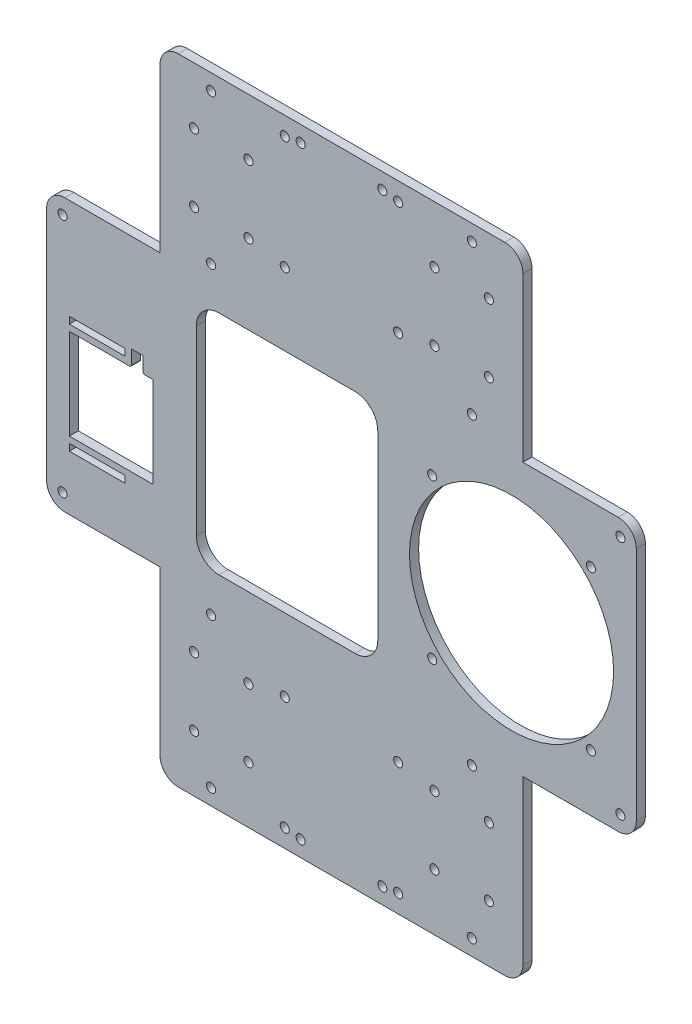
SolidWorks part; units mm, degrees
ref_plane "前视基准面" through (0, 0, 0) normal (0, 0, 1) x (1, 0, 0)
ref_plane "上视基准面" through (0, 0, 0) normal (0, 1, 0) x (1, 0, 0)
ref_plane "右视基准面" through (0, 0, 0) normal (1, 0, 0) x (0, 0, -1)
sketch "草图1" plane through (0, 0, 0) normal (0, 0, 1) x (1, 0, 0)
  line L0 (-71.9312, -82.8481) -> (-47.9312, -82.8481)
  line L1 (-136.9312, 142.1519) -> (123.0688, 142.1519)
  line L2 (-136.9312, 142.1519) -> (-136.9312, -137.8481)
  line L3 (-136.9312, -137.8481) -> (123.0688, -137.8481)
  line L4 (123.0688, 142.1519) -> (123.0688, -137.8481)
  line L5 (-86.9312, 142.1519) -> (73.0688, 142.1519)
  line L6 (-86.9312, 142.1519) -> (-86.9312, 62.1519)
  line L7 (-86.9312, -137.8481) -> (73.0688, -137.8481)
  line L8 (73.0688, 142.1519) -> (73.0688, 62.1519)
  line L9 (-136.9312, -57.8481) -> (-86.9312, -57.8481)
  line L10 (-136.9312, -57.8481) -> (-136.9312, 62.1519)
  line L11 (-136.9312, 62.1519) -> (-86.9312, 62.1519)
  line L12 (123.0688, -57.8481) -> (123.0688, 62.1519)
  line L13 (-71.9312, -82.8481) -> (-71.9312, -112.8481)
  line L14 (-71.9312, -112.8481) -> (-47.9312, -112.8481)
  line L15 (-47.9312, -82.8481) -> (-47.9312, -112.8481)
  line L16 (34.0688, -82.8481) -> (58.0688, -82.8481)
  line L17 (34.0688, -82.8481) -> (34.0688, -112.8481)
  line L18 (34.0688, -112.8481) -> (58.0688, -112.8481)
  line L19 (58.0688, -82.8481) -> (58.0688, -112.8481)
  line L20 (34.0688, 117.1519) -> (58.0688, 117.1519)
  line L21 (34.0688, 117.1519) -> (34.0688, 87.1519)
  line L22 (34.0688, 87.1519) -> (58.0688, 87.1519)
  line L23 (58.0688, 117.1519) -> (58.0688, 87.1519)
  line L24 (-71.9312, 117.1519) -> (-47.9312, 117.1519)
  line L25 (-71.9312, 117.1519) -> (-71.9312, 87.1519)
  line L26 (-71.9312, 87.1519) -> (-47.9312, 87.1519)
  line L27 (-47.9312, 117.1519) -> (-47.9312, 87.1519)
  line L28 (-86.9312, -57.8481) -> (-86.9312, -137.8481)
  line L29 (73.0688, 62.1519) -> (123.0688, 62.1519)
  line L30 (73.0688, -57.8481) -> (73.0688, -137.8481)
  line L31 (73.0688, -57.8481) -> (123.0688, -57.8481)
  line L32 (33.0688, -32.8481) -> (103.0688, -32.8481)
  line L33 (33.0688, -32.8481) -> (33.0688, 37.1519)
  line L34 (33.0688, 37.1519) -> (103.0688, 37.1519)
  line L35 (103.0688, -32.8481) -> (103.0688, 37.1519)
  line L36 (-136.9312, 2.1519) -> (123.0688, 2.1519)
  line L37 (-124.9312, 17.9019) -> (-89.9312, 17.9019)
  line L38 (-124.9312, 17.9019) -> (-124.9312, -33.5981)
  line L39 (-124.9312, -33.5981) -> (-89.9312, -33.5981)
  line L40 (-89.9312, 17.9019) -> (-89.9312, -33.5981)
  line L41 (-124.9312, 17.9019) -> (-89.9312, 17.9019)
  line L42 (-124.9312, 17.9019) -> (-124.9312, 14.9019)
  line L43 (-124.9312, 14.9019) -> (-89.9312, 14.9019)
  line L44 (-89.9312, 17.9019) -> (-89.9312, 14.9019)
  line L45 (-124.9312, 12.1519) -> (-89.9312, 12.1519)
  line L46 (-124.9312, 12.1519) -> (-124.9312, -27.8481)
  line L47 (-124.9312, -27.8481) -> (-89.9312, -27.8481)
  line L48 (-89.9312, 12.1519) -> (-89.9312, -27.8481)
  line L49 (-124.9312, -33.5981) -> (-89.9312, -33.5981)
  line L50 (-124.9312, -33.5981) -> (-124.9312, -30.5981)
  line L51 (-124.9312, -30.5981) -> (-89.9312, -30.5981)
  line L52 (-89.9312, -33.5981) -> (-89.9312, -30.5981)
  line L58 (-31.9312, -79.8481) -> (18.0688, -79.8481)
  line L63 (-64.4312, 135.1519) -> (50.5688, 135.1519)
  line L64 (-64.4312, 135.1519) -> (-64.4312, 69.1519)
  line L65 (-64.4312, 69.1519) -> (50.5688, 69.1519)
  line L66 (50.5688, 135.1519) -> (50.5688, 69.1519)
  line L67 (-64.4312, -64.8481) -> (50.5688, -64.8481)
  line L68 (50.5688, -130.8481) -> (50.5688, -64.8481)
  line L69 (-64.4312, -130.8481) -> (50.5688, -130.8481)
  line L70 (-64.4312, -130.8481) -> (-64.4312, -64.8481)
  line L99 (-31.9312, -79.8481) -> (-31.9312, -129.8481)
  line L100 (-31.9312, -129.8481) -> (18.0688, -129.8481)
  line L101 (18.0688, -79.8481) -> (18.0688, -129.8481)
  circle A0 centre (68.0688, 2.1519) radius 45
  circle A1 centre (-64.4312, 135.1519) radius 2
  circle A2 centre (50.5688, 135.1519) radius 2
  circle A3 centre (-64.4312, 69.1519) radius 2
  circle A4 centre (50.5688, 69.1519) radius 2
  circle A5 centre (33.0688, 37.1519) radius 2
  circle A6 centre (103.0688, 37.1519) radius 2
  circle A7 centre (103.0688, -32.8481) radius 2
  circle A8 centre (33.0688, -32.8481) radius 2
  circle A9 centre (-47.9312, -82.8481) radius 2
  circle A10 centre (-71.9312, -82.8481) radius 2
  circle A11 centre (-71.9312, -112.8481) radius 2
  circle A12 centre (-47.9312, -112.8481) radius 2
  circle A13 centre (34.0688, -82.8481) radius 2
  circle A14 centre (58.0688, -82.8481) radius 2
  circle A15 centre (34.0688, -112.8481) radius 2
  circle A16 centre (58.0688, -112.8481) radius 2
  circle A17 centre (-71.9312, 117.1519) radius 2
  circle A19 centre (-71.9312, 87.1519) radius 2
  circle A20 centre (-47.9312, 87.1519) radius 2
  circle A21 centre (34.0688, 117.1519) radius 2
  circle A22 centre (34.0688, 87.1519) radius 2
  circle A23 centre (58.0688, 117.1519) radius 2
  circle A24 centre (58.0688, 87.1519) radius 2
  circle A25 centre (-47.9312, 117.1519) radius 2
  circle A26 centre (50.5688, -130.8481) radius 2
  circle A27 centre (50.5688, -64.8481) radius 2
  circle A28 centre (-64.4312, -64.8481) radius 2
  circle A29 centre (-64.4312, -130.8481) radius 2
  circle A34 centre (-31.9312, -129.8481) radius 2
  circle A35 centre (18.0688, -129.8481) radius 2
  circle A36 centre (18.0688, -79.8481) radius 2
  circle A37 centre (-31.9312, -79.8481) radius 2
  point P34 (123.0688, 2.1519)
  point P39 (34.0688, 102.1519)
  point P40 (-47.9312, 102.1519)
  point P41 (-86.9312, 102.1519)
  point P42 (-71.9312, 102.1519)
  point P43 (73.0688, 102.1519)
  point P44 (58.0688, 102.1519)
  point P45 (-86.9312, -97.8481)
  point P46 (-71.9312, -97.8481)
  point P47 (34.0688, -97.8481)
  point P48 (-47.9312, -97.8481)
  point P49 (73.0688, -97.8481)
  point P50 (58.0688, -97.8481)
  point P51 (-59.9312, 87.1519)
  point P52 (-59.9312, -82.8481)
  point P53 (46.0688, 87.1519)
  point P54 (46.0688, -82.8481)
  point P55 (103.0688, 2.1519)
  point P68 (-29.8199, 6.0045)
  point P83 (-6.9312, 135.1519)
  point P84 (-6.9312, 142.1519)
  point P85 (-64.4312, 102.1519)
  dimension "D33" = 30
  dimension "D26" = 30
  dimension "D1" = 160
  dimension "D2" = 120
  dimension "D3" = 260
  dimension "D4" = 50
  dimension "D5" = 80
  dimension "D6" = 280
  dimension "D7" = 55
  dimension "D8" = 70
  dimension "D9" = 70
  dimension "D10" = 24
  dimension "D11" = 30
  dimension "D12" = 20
  dimension "D13" = 15
  dimension "D14" = 15
  dimension "D15" = 3
  dimension "D16" = 3
  dimension "D17" = 40
  dimension "D18" = 51.5
  dimension "D19" = 2.75
  dimension "D20" = 35
  dimension "D21" = 12
  dimension "D22" = 30
  dimension "D23" = 50
  dimension "D24" = 50
  dimension "D25" = 8
  dimension "D27" = 24
  dimension "D28" = 66
  dimension "D29" = 115
  dimension "D34" = 24
  dimension "D35" = 30
  dimension "D36" = 24
extrude "凸台-拉伸3" add sketch "草图1" along normal blind 4 contours A6 L35 A0 L36 L4 L29 L8 L1 L6 L11 L2 L38 L37 L40 L33 A5 L34 A24 L22 L66 A4 L65 A3 L64 L26 A19 L25 A17 L24 A1 L63 A2 L20 A23 L23 | A19 L26 L64 L24 A17 L25 | A25 L24 L64 L26 A20 L27 | A25 L27 A20 L26 L64 A3 L65 A4 L66 L22 A22 L21 A21 L20 A2 L63 A1 L24 | A22 L22 L66 L20 A21 L21 | A24 L23 A23 L20 L66 L22 | L38 L45 L40 L43 | L38 L51 L40 L47 | A8 L33 A0 L36 L40 L39 L38 L10 L9 L28 L3 L30 L31 L12 L35 A7 L32 A35 L69 A34 A29 L70 L14 A11 L13 A10 L0 A28 L67 A27 L68 L16 A14 L19 A16 L18 A26 | A37 L58 A36 L101 A35 L69 A26 L68 L18 A15 L17 A13 L16 A27 L67 A28 L70 L0 A9 L15 A12 L14 A29 A34 L99 | A35 L100 A34 L69 | A11 L14 L70 L0 A10 L13 | A12 L15 A9 L0 L70 L14 | A37 L99 A34 L100 A35 L101 A36 L58 | A15 L18 L68 L16 A13 L17 | A16 L19 A14 L16 L68 L18 | A8 L32 A0 L33 | A7 L35 A0 L32 | A5 L33 A0 L34 | A6 L34 A0 L35 region at (-68.0978, -97.8481, 0) region at (-63.1053, -74.8481, 0) region at (-56.2763, -97.8481, 0) region at (-6.9312, -130.349, 0) region at (-6.9312, -104.8481, 0) region at (42.414, -97.8481, 0) region at (54.2355, -97.8481, 0) region at (-18.314, 54.8649, 0) region at (-14.366, -51.7315, 0) region at (-107.4312, 13.5269, 0) region at (-107.4312, -29.2231, 0) region at (35.4588, 34.7619, 0) region at (35.4588, -30.4581, 0) region at (100.6788, 34.7619, 0) region at (100.6788, -30.4581, 0) region at (-6.9312, 102.1519, 0) region at (42.414, 102.1519, 0) region at (54.2355, 102.1519, 0) region at (-68.0978, 102.1519, 0) region at (-56.2763, 102.1519, 0)
fillet "圆角1" radius 8 8 edges at (-136.9312, -57.8481, 2) (-86.9312, -137.8481, 2) (73.0688, -137.8481, 2) (123.0688, -57.8481, 2) (123.0688, 62.1519, 2) (73.0688, 142.1519, 2) (-86.9312, 142.1519, 2) (-136.9312, 62.1519, 2)
sketch "草图4" plane through (0, 0, 4) normal (0, 0, 1) x (1, 0, 0)
  line L0 (-128.9312, 62.1519) -> (-86.9312, 62.1519) construction
  line L1 (-136.9312, 54.1519) -> (-136.9312, -49.8481) construction
  line L2 (-128.9312, -57.8481) -> (-86.9312, -57.8481) construction
  line L3 (73.0688, 62.1519) -> (115.0688, 62.1519) construction
  line L4 (123.0688, 54.1519) -> (123.0688, -49.8481) construction
  line L5 (73.0688, -57.8481) -> (115.0688, -57.8481) construction
  line L6 (-86.9312, 134.1519) -> (-86.9312, 62.1519) construction
  line L9 (-86.9312, -57.8481) -> (-86.9312, -129.8481) construction
  line L11 (-78.9312, -137.8481) -> (65.0688, -137.8481) construction
  line L12 (-78.9312, 142.1519) -> (65.0688, 142.1519) construction
  circle A0 centre (-129.9312, 55.1519) radius 2
  circle A1 centre (-129.9312, -50.8481) radius 2
  circle A2 centre (116.0688, 55.1519) radius 2
  circle A3 centre (116.0688, -50.8481) radius 2
  circle A9 centre (-24.9312, 135.1519) radius 2
  circle A10 centre (11.0688, 135.1519) radius 2
  circle A11 centre (-24.9312, -130.8481) radius 2
  circle A12 centre (11.0688, -130.8481) radius 2
  dimension "D9" = 36
  dimension "D1" = 7
  dimension "D2" = 7
  dimension "D3" = 7
  dimension "D4" = 7
  dimension "D5" = 7
  dimension "D6" = 7
  dimension "D7" = 7
  dimension "D8" = 7
  dimension "D10" = 36
  dimension "D11" = 62
  dimension "D12" = 62
  dimension "D13" = 7
  dimension "D14" = 7
  dimension "D15" = 7
  dimension "D16" = 7
extrude "切除-拉伸3" cut sketch "草图4" against normal blind 4
sketch "草图6" plane through (0, 0, 4) normal (0, 0, 1) x (1, 0, 0)
  line L0 (-78.9312, 142.1519) -> (65.0688, 142.1519) construction
  line L1 (-31.9312, 134.1519) -> (18.0688, 134.1519)
  line L2 (-31.9312, 134.1519) -> (-31.9312, 84.1519)
  line L3 (-31.9312, 84.1519) -> (18.0688, 84.1519)
  line L4 (18.0688, 134.1519) -> (18.0688, 84.1519)
  line L6 (-31.9312, 99.1519) -> (18.0688, 99.1519)
  line L7 (-31.9312, 99.1519) -> (-31.9312, 49.1519)
  line L8 (-31.9312, 49.1519) -> (18.0688, 49.1519)
  line L9 (18.0688, 99.1519) -> (18.0688, 49.1519)
  circle A0 centre (-31.9312, 134.1519) radius 2
  circle A1 centre (18.0688, 134.1519) radius 2
  circle A2 centre (-31.9312, 99.1519) radius 2
  circle A3 centre (18.0688, 99.1519) radius 2
  circle A4 centre (-31.9312, 84.1519) radius 2
  circle A5 centre (-31.9312, 49.1519) radius 2
  circle A6 centre (18.0688, 49.1519) radius 2
  circle A7 centre (18.0688, 84.1519) radius 2
  point P6 (-6.9312, 142.1519)
  point P7 (-6.9312, 134.1519)
  dimension "D1" = 8
  dimension "D2" = 50
  dimension "D3" = 50
  dimension "D4" = 50
  dimension "D5" = 50
  dimension "D6" = 43
extrude "切除-拉伸5" cut sketch "草图6" against normal blind 10 contours L1 A0 L2 | L2 A0 L1 | L4 A1 L1 | L1 A1 L4 | L2 A4 L7 | L3 A4 L2 | L7 A4 L3 | L9 A7 L4 | L4 A7 L3 | L3 A7 L9 region at (-32.2141, 134.4348, 4) region at (-31.0824, 133.3031, 4) region at (18.3518, 134.4348, 4) region at (17.22, 133.3031, 4) region at (-31.0824, 85.0007, 4) region at (-32.78, 84.1519, 4) region at (-31.0824, 83.3031, 4) region at (18.9176, 84.1519, 4) region at (17.22, 85.0007, 4) region at (17.22, 83.3031, 4)
sketch "草图7" plane through (0, 0, 4) normal (0, 0, 1) x (1, 0, 0)
  line L0 (123.0688, 54.1519) -> (123.0688, -49.8481) construction
  line L1 (-70.9312, 52.1519) -> (9.0688, 52.1519)
  line L2 (-70.9312, 52.1519) -> (-70.9312, -47.8481)
  line L3 (-70.9312, -47.8481) -> (9.0688, -47.8481)
  line L4 (9.0688, 52.1519) -> (9.0688, -47.8481)
  line L5 (-136.9312, 54.1519) -> (-136.9312, -49.8481) construction
  point P4 (9.0688, 2.1519)
  point P7 (123.0688, 2.1519)
  dimension "D1" = 80
  dimension "D2" = 100
  dimension "D3" = 66
extrude "切除-拉伸6" cut sketch "草图7" against normal blind 10
fillet "圆角2" radius 10 4 edges at (9.0688, 52.1519, 2) (9.0688, -47.8481, 2) (-70.9312, -47.8481, 2) (-70.9312, 52.1519, 2)
sketch "草图8" plane through (0, 0, 0) normal (0, 0, -1) x (-1, 0, 0)
  line L0 (124.9312, -33.5981) -> (89.9312, -33.5981) construction
  line L1 (106.9312, -33.5981) -> (86.9312, -33.5981)
  line L2 (106.9312, -33.5981) -> (106.9312, 19.1519)
  line L3 (106.9312, 19.1519) -> (86.9312, 19.1519)
  line L4 (86.9312, -33.5981) -> (86.9312, 19.1519)
  line L5 (89.9312, 12.1519) -> (106.9312, 12.1519)
  line L6 (124.9312, 12.1519) -> (89.9312, 12.1519) construction
  line L7 (106.9312, 12.1519) -> (86.9312, 12.1519)
  line L8 (89.9312, 12.1519) -> (89.9312, -27.8481) construction
  line L9 (102.4312, 19.1519) -> (102.4312, 12.1519)
  line L10 (94.4312, 19.1519) -> (99.4312, 19.1519)
  line L11 (94.4312, 19.1519) -> (94.4312, 12.1519)
  line L12 (94.4312, 12.1519) -> (99.4312, 12.1519)
  line L13 (99.4312, 19.1519) -> (99.4312, 12.1519)
  line L16 (102.4312, 12.1519) -> (102.4312, -33.5981)
  line L17 (106.9312, 12.1519) -> (89.9312, 12.1519)
  line L18 (106.9312, 12.1519) -> (106.9312, -27.8481)
  line L19 (106.9312, -27.8481) -> (89.9312, -27.8481)
  line L20 (89.9312, 12.1519) -> (89.9312, -27.8481)
  dimension "D1" = 20
  dimension "D2" = 3
  dimension "D3" = 7
  dimension "D4" = 7.5
  dimension "D5" = 5
  dimension "D6" = 3
extrude "凸台-拉伸5" add sketch "草图8" against normal blind 4 contours L11 L3 L4 L7 L5 | L20 L7 L4 L1 L16 L19 | L3 L13 L5 L9 region at (-94.6812, -33.115, 0) region at (-90.6812, 15.6519, 0) region at (-100.9312, 15.6519, 0)
extrude "切除-拉伸7" cut sketch "草图8<4>" against normal blind 4 contours L13 L3 L11 L7 region at (-96.9312, 15.6519, 0)
sketch "草图8<4>" plane through (0, 0, 0) normal (0, 0, -1) x (-1, 0, 0) same geometry as "草图8"
sketch "草图9" plane through (0, 0, 0) normal (0, 0, -1) x (-1, 0, 0)
  line L0 (124.9312, 14.9019) -> (102.4312, 14.9019) construction
  line L1 (124.9312, 17.9019) -> (126.9312, 17.9019)
  line L2 (124.9312, 17.9019) -> (124.9312, 14.9019)
  line L3 (124.9312, 14.9019) -> (126.9312, 14.9019)
  line L4 (126.9312, 17.9019) -> (126.9312, 14.9019)
  line L5 (124.9312, -33.5981) -> (126.9312, -33.5981)
  line L6 (124.9312, -33.5981) -> (124.9312, -30.5981)
  line L7 (124.9312, -30.5981) -> (126.9312, -30.5981)
  line L8 (126.9312, -33.5981) -> (126.9312, -30.5981)
  line L9 (124.9312, 12.1519) -> (126.9312, 12.1519)
  line L10 (124.9312, 12.1519) -> (124.9312, -27.8481)
  line L11 (124.9312, -27.8481) -> (126.9312, -27.8481)
  line L12 (126.9312, 12.1519) -> (126.9312, -27.8481)
  line L13 (124.9312, -27.8481) -> (89.9312, -27.8481) construction
  line L14 (124.9312, -30.5981) -> (102.4312, -30.5981) construction
  dimension "D1" = 2
  dimension "D2" = 2
  dimension "D3" = 2
extrude "切除-拉伸8" cut sketch "草图9" against normal blind 4
fillet "圆角3" radius 1 2 edges at (-99.4312, 12.1519, 2) (-94.4312, 12.1519, 2)
